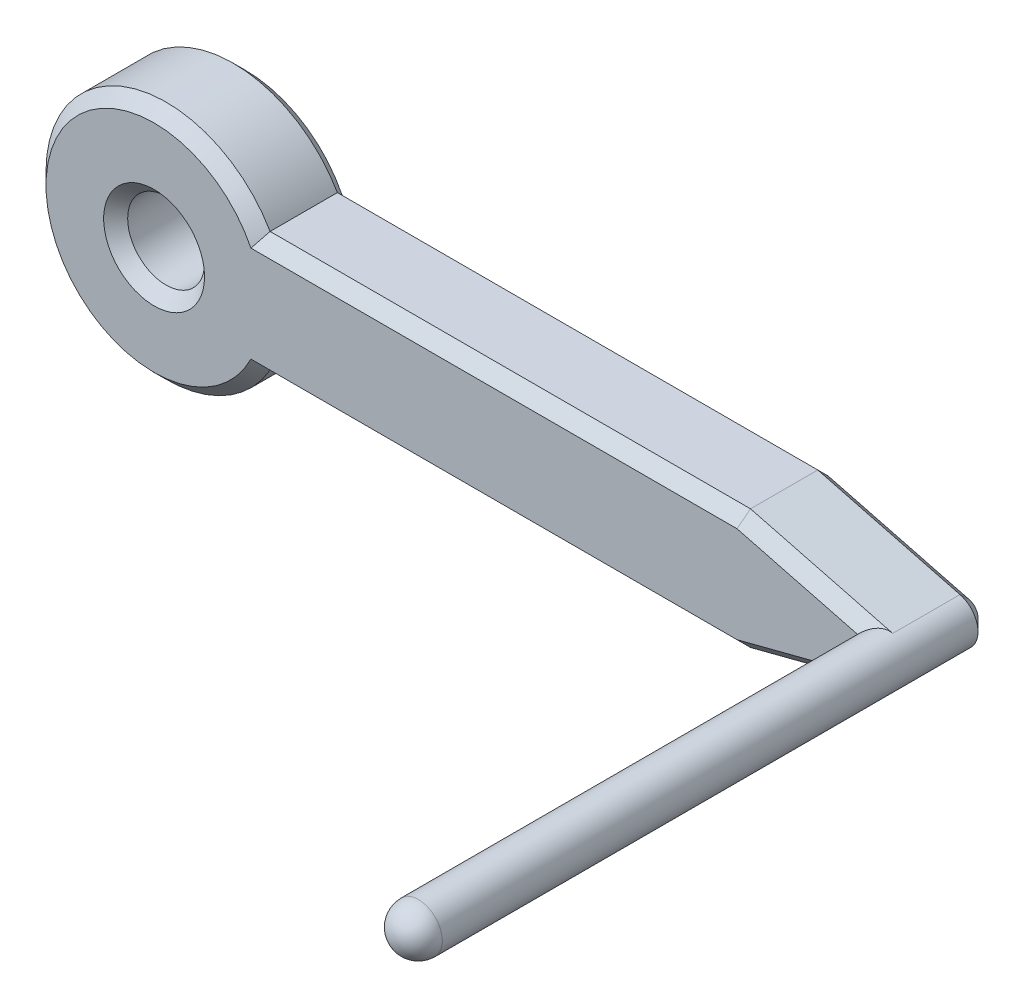
SolidWorks part; units mm, degrees
ref_plane "Front Plane" through (0, 0, 0) normal (0, 0, 1) x (1, 0, 0)
ref_plane "Top Plane" through (0, 0, 0) normal (0, 1, 0) x (1, 0, 0)
ref_plane "Right Plane" through (0, 0, 0) normal (1, 0, 0) x (0, 0, -1)
sketch "Sketch1" plane through (0, 0, 0) normal (0, 0, 1) x (1, 0, 0)
  line L0 (4.3301, 2.5) -> (24.3301, 2.5)
  line L1 (24.3301, 2.5) -> (30.2505, 0.9681)
  line L2 (24.3301, -2.5) -> (4.3301, -2.5)
  line L3 (-8.712, 0) -> (13.2362, 0) construction
  line L6 (24.3301, -2.5) -> (30.2505, -0.9681)
  circle A0 centre (0, 0) radius 5 construction
  circle A1 centre (0, 0) radius 1.6
  circle A2 centre (30, 0) radius 1 construction
  arc A4 (4.3301, 2.5) -> (4.3301, -2.5) centre (0, 0) ccw
  arc A5 (30.2505, 0.9681) -> (30.2505, -0.9681) centre (30, 0) cw
  dimension "D1" = 2.5
  dimension "D3" = 30
  dimension "D2" = 2.5
extrude "Boss-Extrude1" add sketch "Sketch1" along normal blind 3.8
sketch "Sketch2" plane through (0, 0, 3.8) normal (0, 0, 1) x (1, 0, 0)
  circle A0 centre (30, 0) radius 1
  point P3 (30, 0)
  point P7 (30, 0)
extrude "Boss-Extrude2" add sketch "Sketch2" along normal blind 20
fillet "Fillet1" radius 1 1 edges at (31, 0, 23.8)
chamfer "Chamfer1" distance 0.5 angle 45 13 edges at (1.6, 0, 0) (14.3301, -2.5, 0) (14.3301, 2.5, 0) (-5, 0, 0) (14.3301, -2.5, 3.8) (14.3301, 2.5, 3.8) (-5, 0, 3.8) (1.6, 0, 3.8) (27.2903, -1.7341, 0) (31, 0, 0) (27.2903, 1.7341, 0) (27.2903, -1.7341, 3.8) (27.2903, 1.7341, 3.8)
